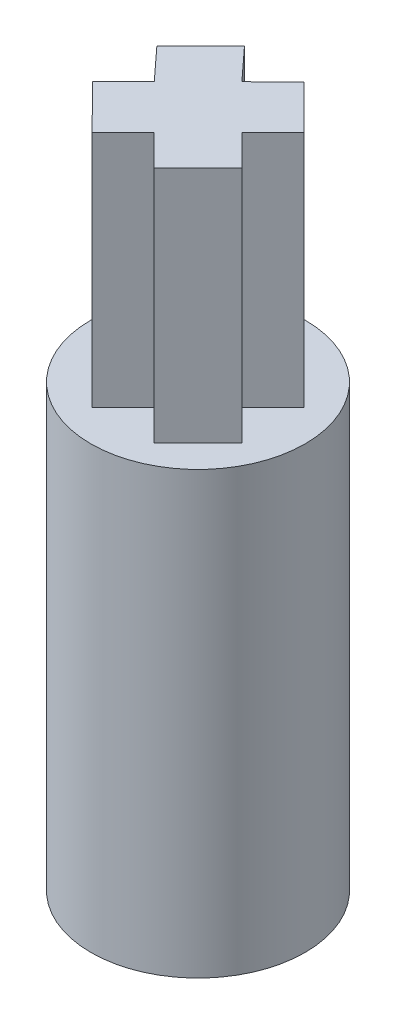
SolidWorks part; units mm, degrees
ref_plane "Front Plane" through (0, 0, 0) normal (0, 0, 1) x (1, 0, 0)
ref_plane "Top Plane" through (0, 0, 0) normal (0, 1, 0) x (1, 0, 0)
ref_plane "Right Plane" through (0, 0, 0) normal (1, 0, 0) x (0, 0, -1)
sketch "Sketch1" plane through (0, 0, 0) normal (0, 1, 0) x (1, 0, 0)
  circle A2 centre (0, 0) radius 5.715
  dimension "D3" = 11.43
extrude "Boss-Extrude1" add sketch "Sketch1" along normal blind 23.495
sketch "Sketch5" plane through (0, 23.495, 0) normal (0, 1, 0) x (1, 0, 0)
  line L0 (0, 2.5411) -> (-1.7512, 4.3809) construction
  line L1 (-2.54, -2.54) -> (2.54, -2.54) construction
  line L2 (-2.54, -2.54) -> (-2.54, 2.54) construction
  line L3 (-2.54, 2.54) -> (2.54, 2.54) construction
  line L4 (2.54, -2.54) -> (2.54, 2.54) construction
  line L5 (-2.54, -2.54) -> (2.54, 2.54) construction
  line L6 (-2.54, 2.54) -> (2.54, -2.54) construction
  line L7 (-2.54, 0.0011) -> (-4.2912, 1.8409) construction
  line L8 (-4.2912, 1.8409) -> (-1.7512, 4.3809) construction
  line L9 (2.54, 0) -> (4.3361, -1.7961) construction
  line L10 (0, -2.54) -> (1.7961, -4.3361) construction
  line L11 (1.7961, -4.3361) -> (4.3361, -1.7961) construction
  line L12 (-2.54, 0.0011) -> (-4.3359, -1.7951) construction
  line L13 (0, -2.54) -> (-1.7964, -4.3357) construction
  line L14 (-4.3359, -1.7951) -> (-1.7964, -4.3357) construction
  line L15 (2.54, 0) -> (4.3364, 1.7957) construction
  line L16 (1.797, 4.3362) -> (4.3364, 1.7957) construction
  line L17 (0, 2.5411) -> (1.797, 4.3362) construction
  line L18 (0, 2.3397) -> (1.6556, 3.9889)
  line L19 (-3.9887, -1.6499) -> (-1.6534, -3.9881)
  line L20 (-3.9181, 1.7234) -> (-1.5813, 4.0602)
  line L21 (0, -2.3368) -> (1.6524, -3.9892)
  line L22 (1.6524, -3.9892) -> (3.9892, -1.6524)
  line L23 (-2.3368, 0.0029) -> (-3.9887, -1.6499)
  line L24 (0, -2.3368) -> (-1.6534, -3.9881)
  line L25 (2.3368, 0) -> (3.9909, 1.6506)
  line L26 (0, 2.3397) -> (-1.5813, 4.0602)
  line L27 (-2.3368, 0.0029) -> (-3.9181, 1.7234)
  line L28 (1.6556, 3.9889) -> (3.9909, 1.6506)
  line L29 (2.3368, 0) -> (3.9892, -1.6524)
  point P0 (0, 0)
  dimension "D1" = 2.54
  dimension "D2" = 5.08
  dimension "D3" = 5.08
  dimension "D4" = 8.6721
  dimension "D5" = 3.5921
  dimension "D6" = 3.5921
  dimension "D7" = 3.5921
  dimension "D8" = 3.5921
  dimension "D9" = 8.6721
  dimension "D10" = 0
  dimension "D11" = 3.5921
  dimension "D12" = 5.08
  dimension "D13" = 2.54
  dimension "D14" = 2.54
  dimension "D15" = 2.54
  dimension "D16" = 2.54
  dimension "D17" = 2.54
  dimension "D18" = 2.54
  dimension "D19" = 2.54
  dimension "D20" = 2.54
extrude "Boss-Extrude3" add sketch "Sketch5" along normal blind 12.7
